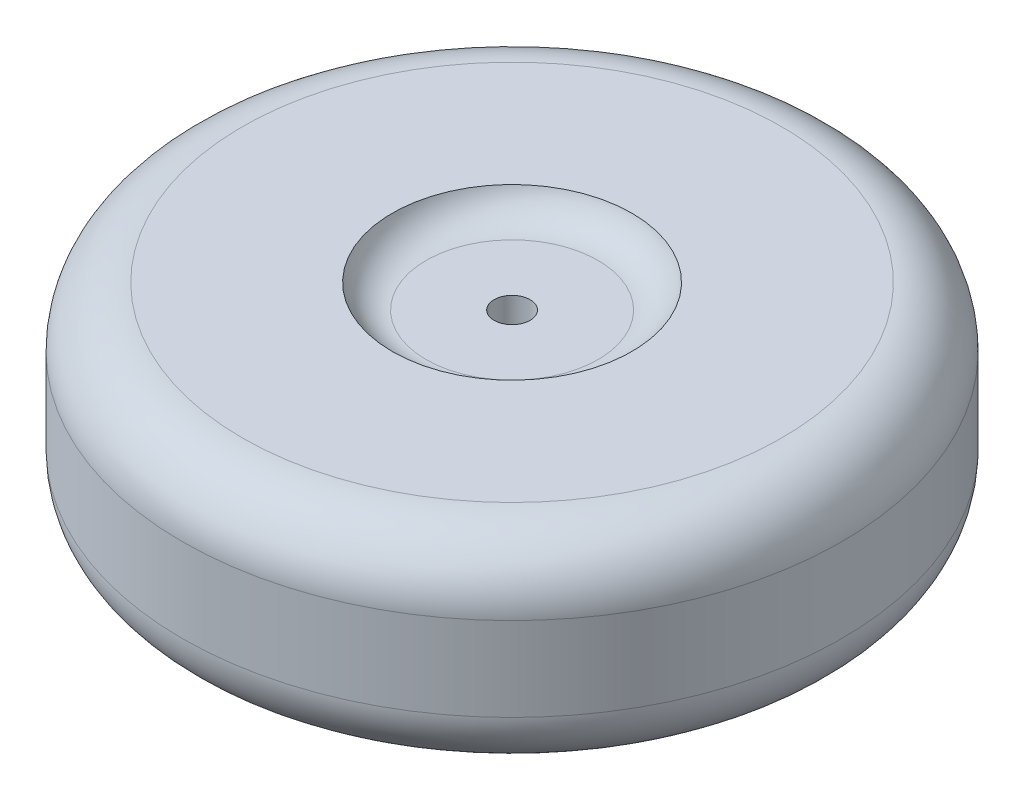
SolidWorks part; units mm, degrees
ref_plane "前视基准面" through (0, 0, 0) normal (0, 0, 1) x (1, 0, 0)
ref_plane "上视基准面" through (0, 0, 0) normal (0, 1, 0) x (1, 0, 0)
ref_plane "右视基准面" through (0, 0, 0) normal (1, 0, 0) x (0, 0, -1)
other "Configuration Table"
sketch "草图1" plane through (0, 0, 0) normal (0, 1, 0) x (1, 0, 0)
  circle A0 centre (0, 0) radius 27.5
extrude "凸台-拉伸1" add sketch "草图1" along normal blind 17
fillet "圆角1" radius 5 2 edges at (0, 17, 27.5) (0, 0, 27.5)
sketch "草图2" plane through (0, 0, 0) normal (0, -1, 0) x (1, 0, 0)
  circle A0 centre (0, 0) radius 1.5
extrude "切除-拉伸1" cut sketch "草图2" against normal through all
sketch "草图3" plane through (0, 17, 0) normal (0, 1, 0) x (1, 0, 0)
  circle A0 centre (0, 0) radius 10
extrude "切除-拉伸2" cut sketch "草图3" against normal blind 2
sketch "草图4" plane through (0, 0, 0) normal (0, -1, 0) x (1, 0, 0)
  circle A1 centre (0, 0) radius 10
  circle A2 centre (0, 0) radius 10
  dimension "D1" = 0
extrude "切除-拉伸3" cut sketch "草图4" against normal blind 2
fillet "圆角2" radius 3 2 edges at (0, 15, 10) (0, 2, -10)
